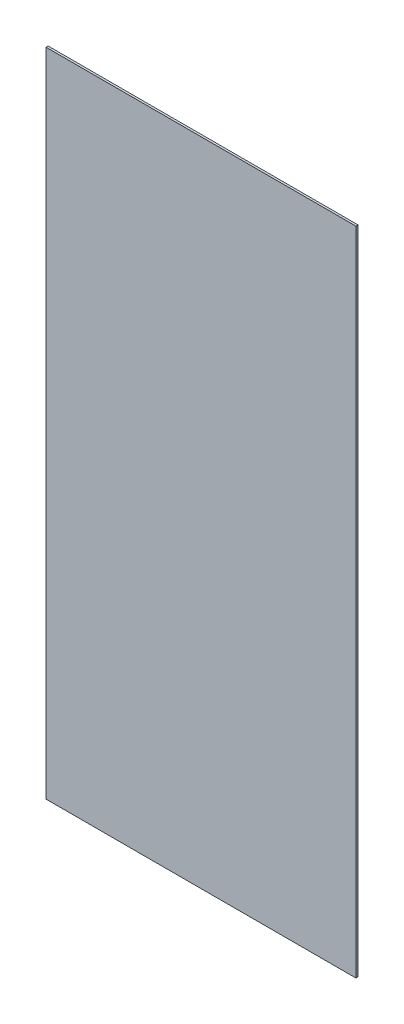
SolidWorks part; units mm, degrees
ref_plane "Front Plane" through (0, 0, 0) normal (0, 0, 1) x (1, 0, 0)
ref_plane "Top Plane" through (0, 0, 0) normal (0, 1, 0) x (1, 0, 0)
ref_plane "Right Plane" through (0, 0, 0) normal (1, 0, 0) x (0, 0, -1)
sketch "Sketch1" plane through (0, 0, 0) normal (0, 0, 1) x (1, 0, 0)
  line L1 (-145, 304.8) -> (145, 304.8)
  line L2 (-145, 304.8) -> (-145, -304.8)
  line L3 (-145, -304.8) -> (145, -304.8)
  line L4 (145, 304.8) -> (145, -304.8)
  line L5 (-145, 304.8) -> (145, -304.8) construction
  line L6 (-145, -304.8) -> (145, 304.8) construction
  point P0 (0, 0)
  point P5 (-8.4994, 0)
  point P6 (0, 0)
  point P7 (0, 0)
  dimension "D1" = 609.6
  dimension "D2" = 290
extrude "Boss-Extrude1" add sketch "Sketch1" along normal blind 2
